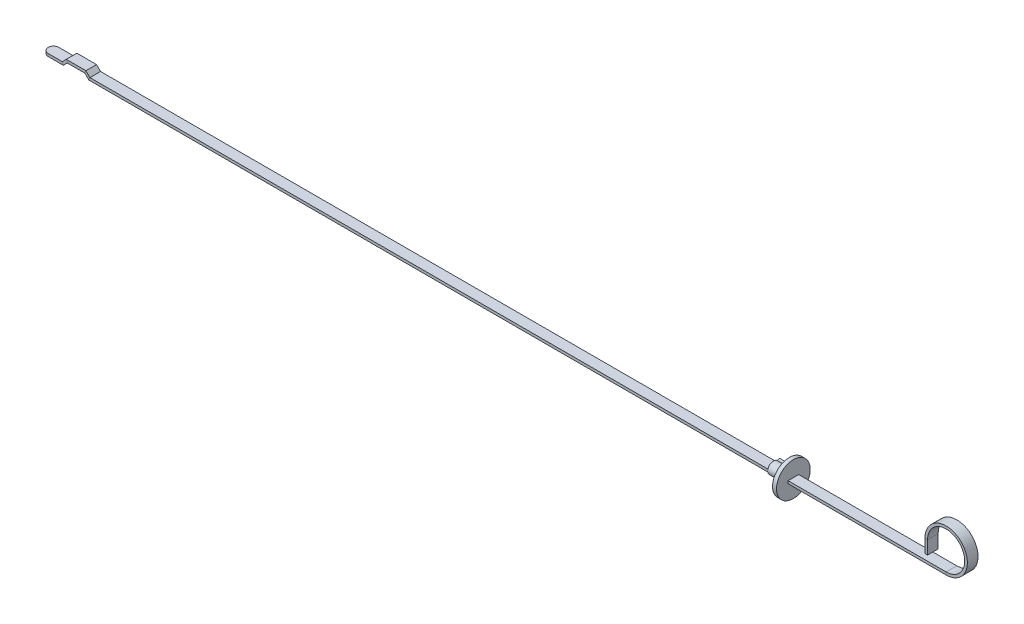
SolidWorks part; units mm, degrees
ref_plane "Płaszczyzna przednia" through (0, 0, 0) normal (0, 0, 1) x (1, 0, 0)
ref_plane "Płaszczyzna górna" through (0, 0, 0) normal (0, 1, 0) x (1, 0, 0)
ref_plane "Płaszczyzna prawa" through (0, 0, 0) normal (1, 0, 0) x (0, 0, -1)
sketch "Szkic1" plane through (0, 0, 0) normal (0, 0, 1) x (1, 0, 0)
  line L0 (0, 0) -> (125, 0)
  line L1 (110, 15) -> (110, 5)
  line L2 (0, 0) -> (-520, 0)
  line L3 (-520, 0) -> (-523, 3)
  line L4 (-523, 3) -> (-537, 3)
  line L5 (-537, 3) -> (-540, 0)
  line L6 (-540, 0) -> (-555, 0)
  arc A0 (125, 0) -> (110, 15) centre (125, 15) ccw
  dimension "D2" = 15
  dimension "D1" = 125
  dimension "D3" = 10
  dimension "D4" = 555
  dimension "D5" = 15
  dimension "D6" = 3
  dimension "D7" = 3
  dimension "D8" = 35
  dimension "D9" = 3
sketch "Szkic5" plane through (0, 0, 0) normal (0, 0, 1) x (1, 0, 0)
  line L1 (0, 6.35) -> (1, 6.35)
  line L3 (0, 0) -> (125, 0) construction
  line L5 (3, 6.35) -> (3, 0)
  line L6 (0, 0) -> (3, 0)
  line L7 (0, 6.35) -> (0, 4.35)
  line L8 (0, 4.35) -> (-9, 4.35)
  line L9 (-9, 4.35) -> (-9, 0)
  line L10 (-9, 0) -> (0, 0)
  arc A0 (1, 6.35) -> (3, 6.35) centre (2, 6.35) ccw
  dimension "D1" = 1
  dimension "D2" = 1
  dimension "D3" = 6.35
  dimension "D4" = 9
  dimension "D5" = 2
revolve "Obrót1" add sketch "Szkic5" angle 360 about L2
sketch "Szkic6" plane through (3, 0, 0) normal (1, 0, 0) x (0, 0, -1)
  circle A0 centre (0, 0) radius 12.7
  dimension "D1" = 25.4
extrude "Dodanie-wyciągnięcie3" add sketch "Szkic6" along normal blind 3
sketch "Szkic7" plane through (0, 0, 0) normal (1, 0, 0) x (0, 0, -1)
  line L1 (-4, -1) -> (4, -1)
  line L2 (-4, -1) -> (-4, 1)
  line L3 (-4, 1) -> (4, 1)
  line L4 (4, -1) -> (4, 1)
  line L5 (-4, -1) -> (4, 1) construction
  line L6 (-4, 1) -> (4, -1) construction
  point P0 (0, 0)
  dimension "D1" = 2
  dimension "D2" = 8
sweep "Wyciągnięcie po ścieżce1" add profiles "Szkic7" path "Szkic1"
fillet "Zaokrąglenie3" radius 4 2 edges at (-555, 0, -4) (-555, 0, 4)
sketch "Szkic13" plane through (-9, 0, 0) normal (-1, 0, 0) x (0, 0, 1)
  line L0 (-1, 0) -> (1, 0)
  line L1 (1, 0) -> (1, -5)
  line L2 (1, -5) -> (-1, -5)
  line L3 (-1, -5) -> (-1, 0)
  point P6 (0, 0)
  dimension "D1" = 5
  dimension "D2" = 2
extrude "Dodanie-wyciągnięcie5" add sketch "Szkic13" against normal blind 2
sketch "Szkic14" plane through (-9, 0, 0) normal (-1, 0, 0) x (0, 0, 1)
  line L0 (-2.946, 3.2006) -> (-4.6319, 3.8142)
  line L1 (-4.6319, 3.8142) -> (-6, 0.0555)
  line L2 (-6, 0.0555) -> (-4.314, -0.5582)
  line L4 (-1, -4.2335) -> (-1, -5) construction
  line L7 (1, -5) -> (1, -4.2335)
  line L8 (-1, -4.2335) -> (-1, -5)
  line L9 (-1, -5) -> (1, -5)
  arc A1 (1, -4.2335) -> (-1, -4.2335) centre (0, 0) ccw
  arc A2 (1, -4.2335) -> (-1, -4.2335) centre (0, 0) ccw construction
  arc A3 (-2.946, 3.2006) -> (-4.314, -0.5582) centre (0, 0) ccw
  point P7 (0, 0)
  point P8 (-5.316, 1.9349)
  point P10 (0, 0)
  point P11 (0, 0)
  point P15 (0, 0)
  point P16 (-6.8775, 4.3637)
  point P17 (-8.2061, 2.0605)
  point P18 (-8.0633, 4.9811)
  point P19 (-7.4502, 3.7403)
  point P20 (-4.3256, -0.4603)
  point P21 (-5.7658, 3.7469)
  point P22 (-5.0399, 4.1958)
  point P24 (-5.401, 4.075)
  dimension "D1" = 110
  dimension "D2" = 4
  dimension "D3" = 6
  dimension "D4" = 0
extrude "Dodanie-wyciągnięcie6" add sketch "Szkic14" against normal blind 5
